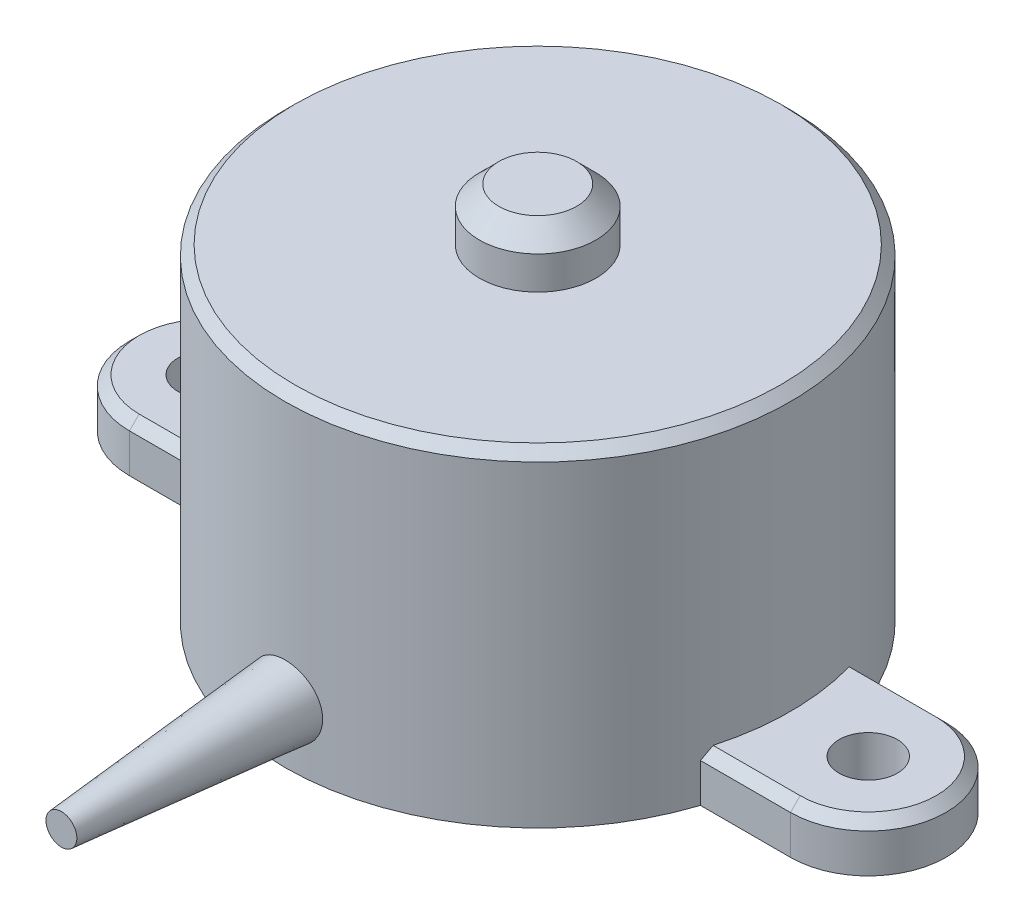
SolidWorks part; units mm, degrees
ref_plane "Front Plane" through (0, 0, 0) normal (0, 0, 1) x (1, 0, 0)
ref_plane "Top Plane" through (0, 0, 0) normal (0, 1, 0) x (1, 0, 0)
ref_plane "Right Plane" through (0, 0, 0) normal (1, 0, 0) x (0, 0, -1)
sketch "Sketch1" plane through (0, 0, 0) normal (0, 1, 0) x (1, 0, 0)
  line L0 (0, -10.725) -> (0, 10.725) construction
  line L1 (-17, 0) -> (17, 0) construction
  line L2 (-10.725, 0) -> (10.725, 0) construction
  line L3 (-17, 4) -> (17, 4)
  line L4 (-17, -4) -> (17, -4)
  circle A0 centre (0, 0) radius 13
  arc A1 (-17, 4) -> (-17, -4) centre (-17, 0) ccw
  arc A2 (17, -4) -> (17, 4) centre (17, 0) ccw
  circle A3 centre (-17, 0) radius 1.5
  circle A4 centre (17, 0) radius 1.5
  point P9 (0, 0)
  dimension "D1" = 4
  dimension "D3" = 26
  dimension "D4" = 3
  dimension "D5" = 3
  dimension "D2" = 34
extrude "Boss-Extrude1" add sketch "Sketch1" along normal blind 2.5 contours A3 A0 L3 A1 L4 | A0 L1 L3 | L1 A0 L4 | L3 A0 | L4 A0 | L4 A2 L3 A0 A4 region at (-12.9576, 0, 2.043) region at (0, 0, -1.9836) region at (0, 0, 1.9836) region at (12.9576, 0, -2.043) region at (0, 0, -7.7342) region at (0, 0, 7.7342)
sketch "Sketch2" plane through (0, 2.5, 0) normal (0, 1, 0) x (1, 0, 0)
  circle A0 centre (0, 0) radius 13
extrude "Boss-Extrude2" add sketch "Sketch2" along normal offset from surface (14.3 mm away) 16.8 up to face at (0, 0, 0)
sketch "Sketch3" plane through (0, 16.8, 0) normal (0, 1, 0) x (1, 0, 0)
  circle A0 centre (0, 0) radius 3
  dimension "D1" = 6
extrude "Boss-Extrude3" add sketch "Sketch3" along normal offset from surface (2.7 mm away) 19.5 up to face at (0, 0, 0)
chamfer "Chamfer1" distance 1 angle 45 1 edges at (0, 19.5, 3)
sketch "Sketch4" plane through (0, 0, 0) normal (0, 0, 1) x (1, 0, 0)
  line L0 (0, -10.725) -> (0, 10.725) construction
  line L1 (20.625, 0) -> (-20.625, 0) construction
  circle A0 centre (0, 3) radius 2.5
  dimension "D1" = 5
  dimension "D2" = 3
extrude "Boss-Extrude4" add sketch "Sketch4" along normal blind 19.5 draft 5 from offset 5
chamfer "Chamfer2" distance 0.5 angle 45 7 edges at (-14.6847, 2.5, -4) (-21, 2.5, 0) (-14.6847, 2.5, 4) (0, 16.8, 13) (14.6847, 2.5, -4) (21, 2.5, 0) (14.6847, 2.5, 4)
